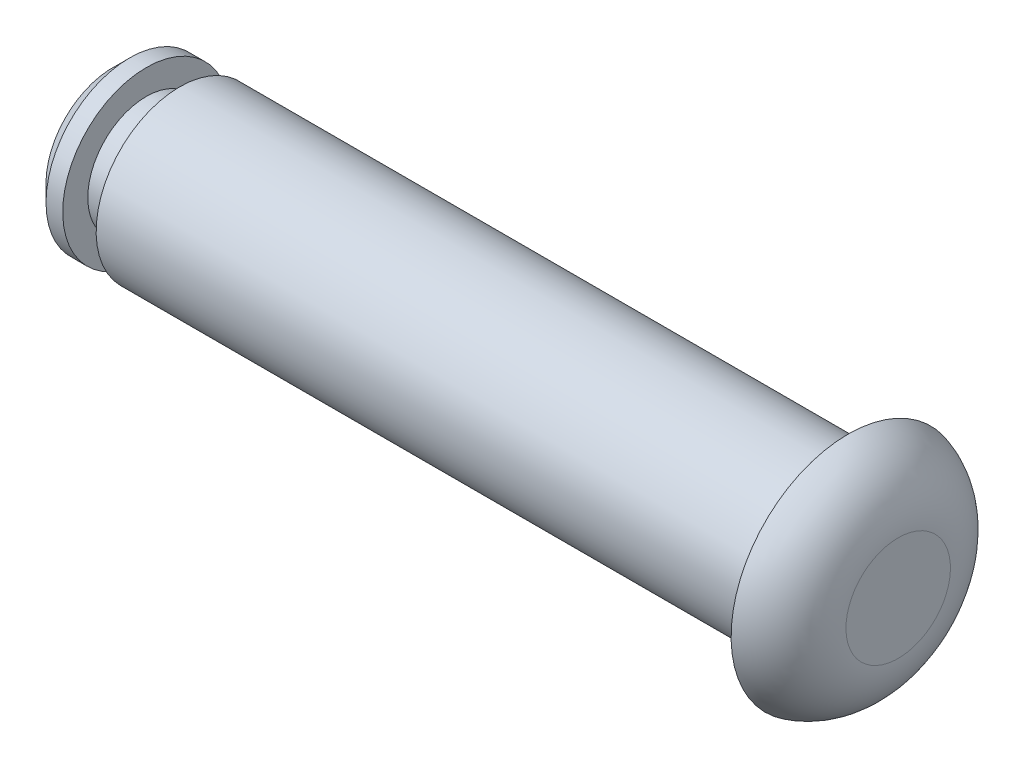
SolidWorks part; units mm, degrees
material "AISI 304"
ref_plane "Front Plane" through (0, 0, 0) normal (0, 0, 1) x (1, 0, 0)
ref_plane "Top Plane" through (0, 0, 0) normal (0, 1, 0) x (1, 0, 0)
ref_plane "Right Plane" through (0, 0, 0) normal (1, 0, 0) x (0, 0, -1)
sketch "Sketch1" plane through (0, 0, 0) normal (0, 0, 1) x (1, 0, 0)
  line L0 (0, 0) -> (0, 2.5)
  line L1 (0, 2.5) -> (1, 2.5)
  line L2 (1, 2.5) -> (1, 1.75)
  line L3 (1, 1.75) -> (2, 1.75)
  line L4 (2, 1.75) -> (2, 2.5)
  line L5 (2, 2.5) -> (22, 2.5)
  line L6 (22, 2.5) -> (22, 3.5)
  line L7 (22, 3.5) -> (23.5, 3.5)
  line L8 (23.5, 3.5) -> (23.5, 0)
  line L9 (23.5, 0) -> (0, 0)
  dimension "D1" = 2.5
  dimension "D2" = 20
  dimension "D3" = 1.5
  dimension "D4" = 1.75
  dimension "D5" = 1
  dimension "D6" = 3.5
  dimension "D7" = 1
revolve "Revolve1" add sketch "Sketch1" angle 360 about L9
fillet "Fillet1" radius 2 1 edges at (23.5, 3.5, 0)
chamfer "Chamfer1" distance 0.5 angle 45 1 edges at (0, 2.5, 0)
